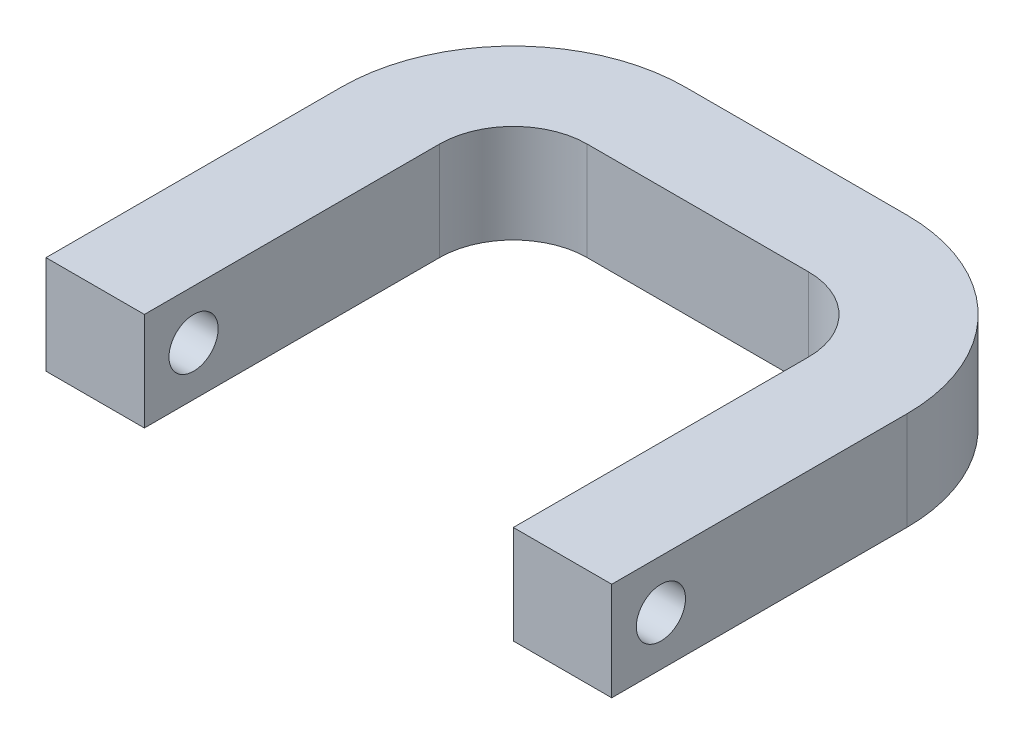
SolidWorks part; units mm, degrees
ref_plane "Front Plane" through (0, 0, 0) normal (0, 0, 1) x (1, 0, 0)
ref_plane "Top Plane" through (0, 0, 0) normal (0, 1, 0) x (1, 0, 0)
ref_plane "Right Plane" through (0, 0, 0) normal (1, 0, 0) x (0, 0, -1)
ref_axis "Z" through (0, 0, -3) along (0, 0, 1)
sketch "Sketch1" plane through (0, 0, 0) normal (0, 1, 0) x (1, 0, 0)
  line L0 (-9, 0) -> (9, 0)
  line L1 (-23, -14) -> (-23, -38)
  line L2 (-23, -38) -> (-15, -38)
  line L3 (-15, -38) -> (-15, -14)
  line L4 (-9, -8) -> (9, -8)
  line L5 (0, -8) -> (0, 0) construction
  line L6 (15, -38) -> (15, -14)
  line L7 (23, -38) -> (15, -38)
  line L8 (23, -14) -> (23, -38)
  arc A0 (-9, 0) -> (-23, -14) centre (-9, -14) ccw
  arc A1 (-15, -14) -> (-9, -8) centre (-9, -14) cw
  arc A2 (15, -14) -> (9, -8) centre (9, -14) ccw
  arc A3 (9, 0) -> (23, -14) centre (9, -14) cw
  point P1 (-24.027, -46.3764)
  point P10 (-21.1789, -15.0832)
  point P13 (-25.4107, -8.4375)
  point P14 (-21.2595, -51.592)
  point P15 (-26.7944, -12.4222)
  point P16 (0, 0)
  point P17 (0, 0)
  point P25 (-35.0781, -49.3823)
  point P26 (-13.4379, -21.5621)
  dimension "D3" = 6
  dimension "D1" = 30
  dimension "D2" = 8
  dimension "D4" = 30
extrude "Boss-Extrude1" add sketch "Sketch1" along normal blind 4 and the other way blind 4
sketch "Sketch2" plane through (15, 0, 0) normal (-1, 0, 0) x (0, 0, 1)
  line L0 (38, -4) -> (38, 4) construction
  line L1 (19.25, 0) -> (-19.25, 0) construction
  circle A0 centre (34, 0) radius 2
  point P4 (55, 0.9476)
  dimension "D1" = 4
  dimension "D2" = 4
extrude "Cut-Extrude1" cut sketch "Sketch2" against normal through all both and the other way through all
equation "\"width\"= 30"
equation "\"prongwidth\"= 8"
equation "\"D2@Sketch1\"=\"prongwidth\""
equation "\"D1@Sketch1\"=\"width\""
equation "\"D3@Sketch1\"=\"width\"/5"
equation "\"pronglength\"= \"width\""
equation "\"D4@Sketch1\"=\"pronglength\""
equation "\"D1@Boss-Extrude1\"=\"prongwidth\"/2"
equation "\"D2@Boss-Extrude1\"=\"prongwidth\"/2"
equation "\"D2@Sketch2\"=\"prongwidth\"/2"
